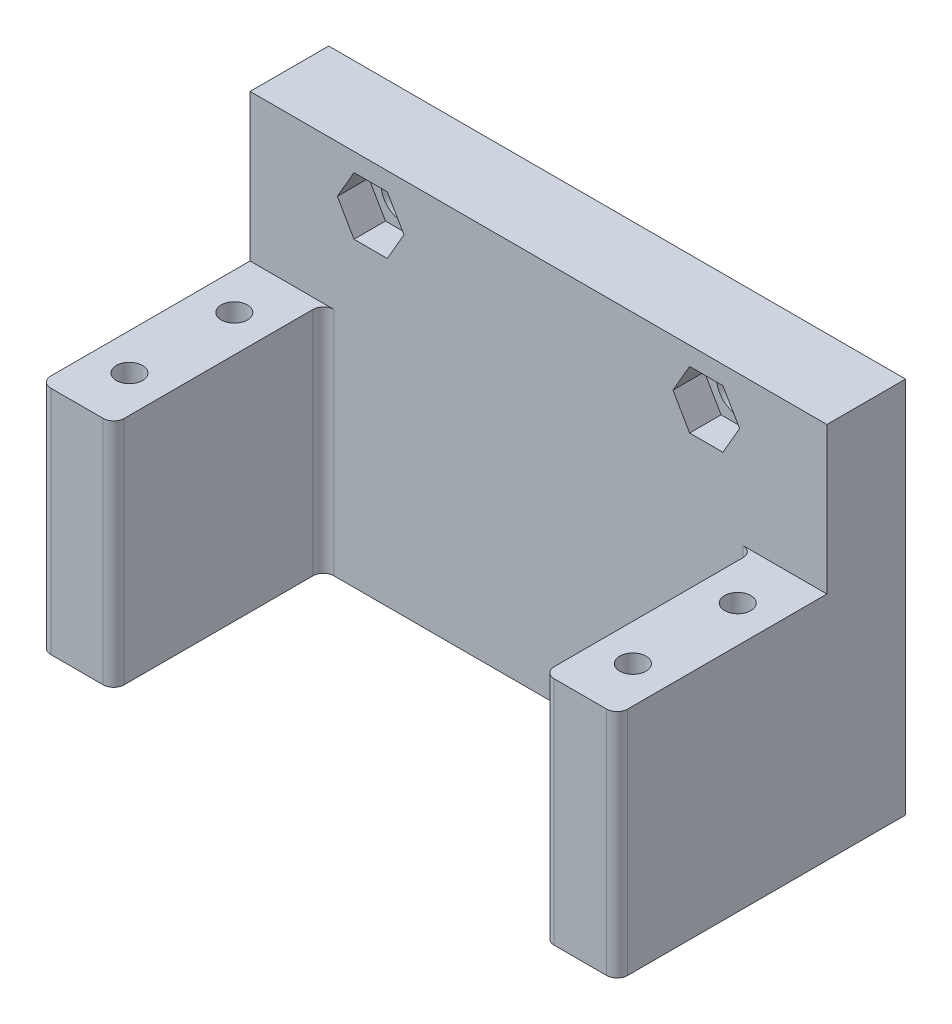
SolidWorks part; units mm, degrees
ref_plane "Front Plane" through (0, 0, 0) normal (0, 0, 1) x (1, 0, 0)
ref_plane "Top Plane" through (0, 0, 0) normal (0, 1, 0) x (1, 0, 0)
ref_plane "Right Plane" through (0, 0, 0) normal (1, 0, 0) x (0, 0, -1)
sketch "Sketch1" plane through (0, 0, 0) normal (0, 0, 1) x (1, 0, 0)
  line L1 (0, 0) -> (55, 0)
  line L2 (0, 0) -> (0, -36)
  line L3 (0, -36) -> (55, -36)
  line L4 (55, 0) -> (55, -36)
  circle A0 centre (11.5, -4.5) radius 2
  circle A1 centre (43.5, -4.5) radius 2
  dimension "D3" = 4.5
  dimension "D1" = 55
  dimension "D2" = 36
  dimension "D4" = 11.5
  dimension "D5" = 2
extrude "Boss-Extrude1" add sketch "Sketch1" along normal blind 7.5
sketch "Sketch2" plane through (0, -36, 0) normal (0, -1, 0) x (1, 0, 0)
  line L1 (0, 7.5) -> (7, 7.5)
  line L2 (0, 7.5) -> (0, 27.5)
  line L3 (0, 27.5) -> (7, 27.5)
  line L4 (7, 7.5) -> (7, 27.5)
  line L5 (55, 7.5) -> (48, 7.5)
  line L6 (55, 7.5) -> (55, 27.5)
  line L7 (55, 27.5) -> (48, 27.5)
  line L8 (48, 7.5) -> (48, 27.5)
  dimension "D1" = 41
  dimension "D2" = 7
  dimension "D3" = 20
extrude "Boss-Extrude2" add sketch "Sketch2" against normal blind 22
sketch "Sketch3" plane through (0, -14, 0) normal (0, 1, 0) x (1, 0, 0)
  line L0 (55, -7.5) -> (0, -7.5) construction
  line L1 (0, -27.5) -> (0, -7.5) construction
  circle A0 centre (3.5, -12.5) radius 1.25
  circle A1 centre (51.5, -12.5) radius 1.25
  circle A2 centre (51.5, -22.5) radius 1.25
  circle A3 centre (3.5, -22.5) radius 1.25
  dimension "D1" = 2
  dimension "D3" = 5
  dimension "D4" = 3.5
  dimension "D2" = 2
extrude "Cut-Extrude1" cut sketch "Sketch3" against normal blind 10
sketch "Sketch4" plane through (0, 0, 7.5) normal (0, 0, 1) x (1, 0, 0)
  line L1 (13.0877, -1.75) -> (9.9123, -1.75)
  line L2 (9.9123, -1.75) -> (8.3246, -4.5)
  line L3 (8.3246, -4.5) -> (9.9123, -7.25)
  line L4 (9.9123, -7.25) -> (13.0877, -7.25)
  line L5 (13.0877, -7.25) -> (14.6754, -4.5)
  line L6 (14.6754, -4.5) -> (13.0877, -1.75)
  circle A0 centre (11.5, -4.5) radius 2.75 construction
extrude "Cut-Extrude2" cut sketch "Sketch4" against normal blind 3
pattern_linear "LPattern1" count 2 spacing 32 along (1, 0, 0) of "Cut-Extrude2"
fillet "Fillet1" radius 1 6 edges at (48, -25, 27.5) (55, -25, 27.5) (7, -25, 27.5) (0, -25, 27.5) (48, -25, 7.5) (7, -25, 7.5)
sketch "Sketch5" plane through (0, 0, 0) normal (0, 1, 0) x (1, 0, 0)
  line L0 (27.5, 0) -> (27.5, -17.5)
  line L1 (55, 0) -> (0, 0) construction
  line L2 (27.5, -17.5) -> (37.5, -17.5)
  line L3 (27.5, 0) -> (27.5, 16)
  line L4 (27.5, 16) -> (37.5, -17.5)
